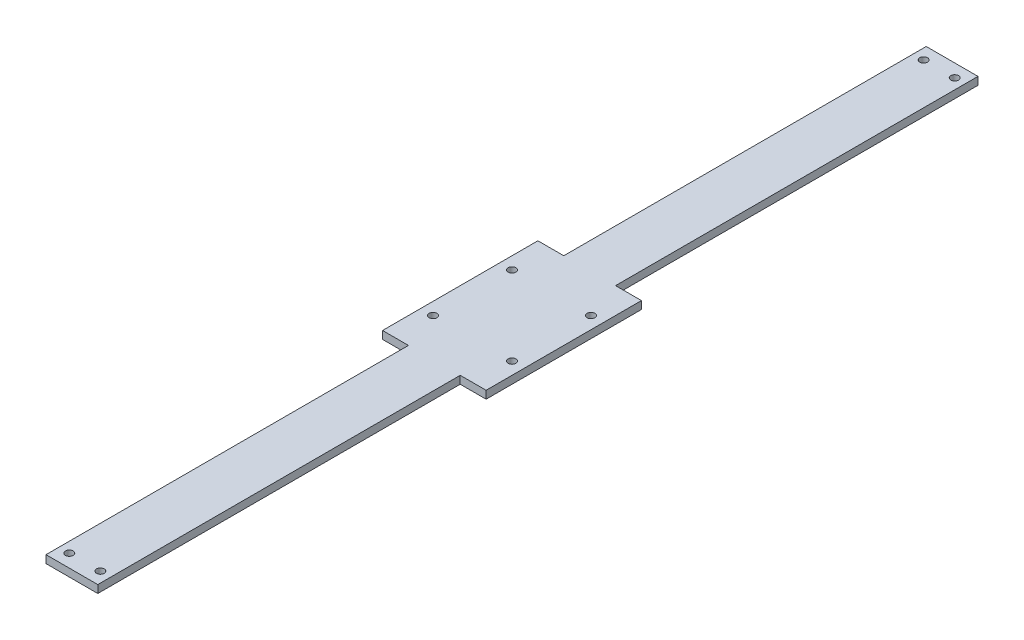
SolidWorks part; units mm, degrees
ref_plane "Front Plane" through (0, 0, 0) normal (0, 0, 1) x (1, 0, 0)
ref_plane "Top Plane" through (0, 0, 0) normal (0, 1, 0) x (1, 0, 0)
ref_plane "Right Plane" through (0, 0, 0) normal (1, 0, 0) x (0, 0, -1)
sketch "Sketch1" plane through (0, 0, 0) normal (0, 1, 0) x (1, 0, 0)
  line L5 (-10, 170) -> (-10, 30)
  line L6 (20, 170) -> (-20, 170) construction
  line L12 (20, 170) -> (20, -170) construction
  line L13 (20, -170) -> (-20, -170) construction
  line L24 (-20, 170) -> (-20, -170) construction
  line L25 (20, 170) -> (-20, -170) construction
  line L26 (20, -170) -> (-20, 170) construction
  line L27 (-10, 30) -> (-20, 30)
  line L28 (0, 170) -> (0, -170) construction
  line L29 (-20, 0) -> (20, 0) construction
  line L30 (10, 30) -> (20, 30)
  line L31 (10, 170) -> (10, 30)
  line L32 (-10, -30) -> (-20, -30)
  line L33 (-10, -170) -> (-10, -30)
  line L34 (10, -170) -> (10, -30)
  line L35 (10, -30) -> (20, -30)
  line L36 (-10, 170) -> (10, 170)
  line L37 (-10, -170) -> (10, -170)
  line L38 (-20, 30) -> (-20, -30)
  line L39 (20, 30) -> (20, -30)
  point P0 (0, 0)
  dimension "D2" = 40
  dimension "D1" = 340
  dimension "D3" = 10
  dimension "D4" = 30
ref_axis "yaw" through (0, 177.4955, 0) along (0, -1, 0)
extrude "Boss-Extrude1" add sketch "Sketch1" along normal mid plane 3
sketch "Sketch4" plane through (0, 1.5, 0) normal (0, 1, 0) x (1, 0, 0)
  line L1 (15.25, 15.25) -> (-15.25, 15.25)
  line L2 (15.25, 15.25) -> (15.25, -15.25)
  line L3 (15.25, -15.25) -> (-15.25, -15.25)
  line L4 (-15.25, 15.25) -> (-15.25, -15.25)
  line L5 (15.25, 15.25) -> (-15.25, -15.25) construction
  line L6 (15.25, -15.25) -> (-15.25, 15.25) construction
  point P0 (0, 0)
  dimension "D1" = 30.5
  dimension "D2" = 30.5
hole_wizard "Ø3.0 (3) Diameter Hole1" positions "Sketch5" profile "Sketch6" hole size "Ø3.0" standard "ISO" end condition through all
sketch "Sketch5" plane through (0, 1.5, 0) normal (0, 1, 0) x (1, 0, 0)
  point P0 (-15.25, 15.25)
  point P3 (15.25, 15.25)
  point P6 (15.25, -15.25)
  point P9 (-15.25, -15.25)
sketch "Sketch6" plane through (-15.25, 1.5, -15.25) normal (1, 0, 0) x (0, 0, 1)
  line L0 (0, 0) -> (0, 3)
  line L1 (0, 3) -> (1.5, 3)
  line L2 (1.5, 3) -> (1.5, 0)
  line L5 (1.5, 0) -> (0, 0)
  line L11 (0, -6.35) -> (0, 107.95) construction
  dimension "Thru Hole Dia." = 3
  dimension "Thru Hole Depth" = 3
sketch "Sketch7" plane through (0, 1.5, 0) normal (0, 1, 0) x (1, 0, 0)
  circle A0 centre (-6, 165) radius 1.5 construction
  circle A1 centre (6, 165) radius 1.5 construction
  circle A2 centre (-6, -165) radius 1.5 construction
  circle A3 centre (6, -165) radius 1.5 construction
  circle A4 centre (-6, 165) radius 1.5
  circle A5 centre (6, 165) radius 1.5
  circle A6 centre (-6, -165) radius 1.5
  circle A7 centre (6, -165) radius 1.5
hole_wizard "Ø3.0 (3) Diameter Hole2" positions "Sketch12" profile "Sketch13" hole size "Ø3.0" standard "ISO" end condition through all
sketch "Sketch12" plane through (0, 1.5, 0) normal (0, 1, 0) x (1, 0, 0)
  point P0 (-6, -165)
  point P3 (6, -165)
  point P6 (-6, 165)
  point P9 (6, 165)
sketch "Sketch13" plane through (-6, 1.5, 165) normal (1, 0, 0) x (0, 0, 1)
  line L0 (0, 0) -> (0, 3)
  line L1 (0, 3) -> (1.5, 3)
  line L2 (1.5, 3) -> (1.5, 0)
  line L5 (1.5, 0) -> (0, 0)
  line L11 (0, -6.35) -> (0, 107.95) construction
  dimension "Thru Hole Dia." = 3
  dimension "Thru Hole Depth" = 3
